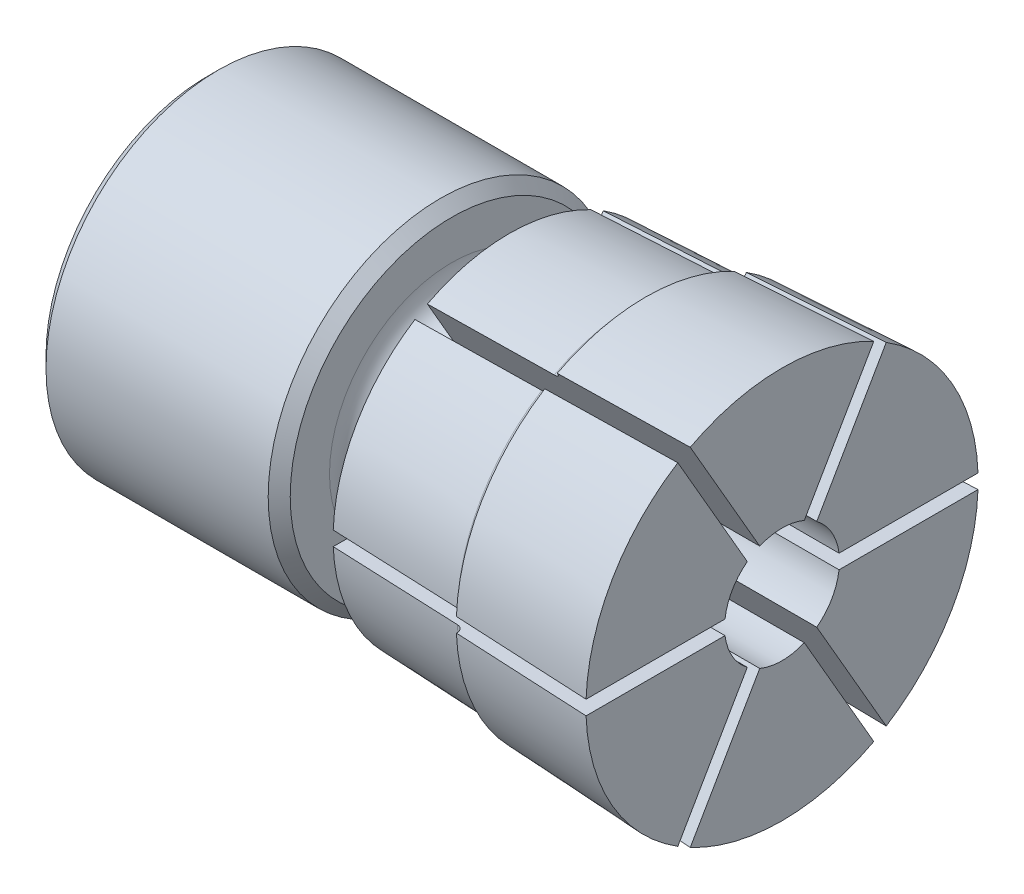
SolidWorks part; units mm, degrees
ref_plane "Front Plane" through (0, 0, 0) normal (0, 0, 1) x (1, 0, 0)
ref_plane "Top Plane" through (0, 0, 0) normal (0, 1, 0) x (1, 0, 0)
ref_plane "Right Plane" through (0, 0, 0) normal (1, 0, 0) x (0, 0, -1)
sketch "Sketch1" plane through (0, 0, 0) normal (0, 0, 1) x (1, 0, 0)
  line L0 (8.054, 0) -> (0, 4.65)
  line L1 (0, 4.65) -> (0, 11.233)
  line L2 (0, 11.233) -> (0.767, 12)
  line L3 (0.767, 12) -> (16.233, 12)
  line L4 (16.233, 12) -> (17, 11.233)
  line L5 (17, 11.233) -> (17, 8.5)
  line L6 (21, 8.5) -> (21, 12.25)
  line L7 (21, 12.25) -> (30.021, 12.6298)
  line L8 (30.5, 13.1294) -> (30.5, 13.175)
  line L9 (30.5, 13.175) -> (40, 13.65)
  line L10 (40, 13.65) -> (40, 0)
  line L11 (40, 0) -> (8.054, 0)
  line L12 (40, 0) -> (8.054, 0) construction
  arc A0 (17, 8.5) -> (21, 8.5) centre (19, 8.5) ccw
  arc A1 (30.021, 12.6298) -> (30.5, 13.1294) centre (30, 13.1294) ccw
revolve "Revolve1" add sketch "Sketch1" angle 360 about L12 reverse direction yes
cosmetic thread "Cosmetic Thread1" parameters "D1"=17, "D2"=22.466
ref_plane "Plane1" through (17.8, 0, 0) normal (1, 0, 0) x (0, 0, -1)
ref_plane "Plane2" through (22.5, 0, 0) normal (1, 0, 0) x (0, 0, -1)
ref_plane "Plane3" through (31, 0, 0) normal (1, 0, 0) x (0, 0, -1)
ref_plane "Plane4" through (33.1, 0, 0) normal (1, 0, 0) x (0, 0, -1)
ref_plane "Plane5" through (41.3, 0, 0) normal (1, 0, 0) x (0, 0, -1)
sketch "Sketch2" plane through (0, 0, 0) normal (1, 0, 0) x (0, 0, -1)
  line L0 (-4, -2.3094) -> (0, -4.6188)
  line L1 (0, -4.6188) -> (4, -2.3094)
  line L2 (4, -2.3094) -> (4, 2.3094)
  line L3 (4, 2.3094) -> (0, 4.6188)
  line L4 (0, 4.6188) -> (-4, 2.3094)
  line L5 (-4, 2.3094) -> (-4, -2.3094)
extrude "Cut-Extrude1" cut sketch "Sketch2" along normal blind 6
sketch "Sketch3" plane through (0, 0, 0) normal (0, 1, 0) x (1, 0, 0)
  line L0 (6, 0) -> (6, 4.75)
  line L1 (6, 4.75) -> (8, 4.75)
  line L2 (8, 4.75) -> (8, 3.5)
  line L3 (8, 3.5) -> (10, 3.5)
  line L4 (10, 3.5) -> (10, 4.2)
  line L5 (10, 4.2) -> (12, 4.2)
  line L6 (12, 4.2) -> (12, 4)
  line L7 (12, 4) -> (42, 4)
  line L8 (42, 4) -> (42, 0)
  line L9 (42, 0) -> (6, 0)
  line L10 (42, 0) -> (6, 0) construction
revolve "Cut-Revolve1" cut sketch "Sketch3" angle 360 about L10 reverse direction yes
ref_plane "Plane6" through (18, 0, 0) normal (1, 0, 0) x (0, 0, -1)
sketch "Sketch4" plane through (18, 0, 0) normal (1, 0, 0) x (0, 0, -1)
  line L0 (-18.65, 0.5) -> (-18.65, -0.5)
  line L1 (-18.65, -0.5) -> (-0.866, -0.5)
  line L2 (-0.866, -0.5) -> (-9.758, -15.9014)
  line L3 (-9.758, -15.9014) -> (-8.892, -16.4014)
  line L4 (-8.892, -16.4014) -> (0, -1)
  line L5 (0, -1) -> (8.892, -16.4014)
  line L6 (8.892, -16.4014) -> (9.758, -15.9014)
  line L7 (9.758, -15.9014) -> (0.866, -0.5)
  line L8 (0.866, -0.5) -> (18.65, -0.5)
  line L9 (18.65, -0.5) -> (18.65, 0.5)
  line L10 (18.65, 0.5) -> (0.866, 0.5)
  line L11 (0.866, 0.5) -> (9.758, 15.9014)
  line L12 (9.758, 15.9014) -> (8.892, 16.4014)
  line L13 (8.892, 16.4014) -> (0, 1)
  line L14 (0, 1) -> (-8.892, 16.4014)
  line L15 (-8.892, 16.4014) -> (-9.758, 15.9014)
  line L16 (-9.758, 15.9014) -> (-0.866, 0.5)
  line L17 (-0.866, 0.5) -> (-18.65, 0.5)
extrude "Cut-Extrude2" cut sketch "Sketch4" along normal blind 40
ref_plane "Plane7" through (40, 0, 0) normal (1, 0, 0) x (0, 0, -1)
ref_plane "ANBAU XY" through (40, 0, 0) normal (1, 0, 0) x (0, 0, -1)
ref_plane "ANBAU XZ" through (0, 0, 0) normal (0, -1, 0) x (-1, 0, 0)
ref_plane "ANBAU YZ" through (0, 0, 0) normal (0, 0, -1) x (-1, 0, 0)
ref_axis "ANBAU X" through (40, 0, 80.9) along (0, 0, -1)
ref_axis "ANBAU Y" through (40, -50, 0) along (0, 1, 0)
ref_axis "ANBAU Z" through (80.9, 0, 0) along (-1, 0, 0)
sketch3d "ANBAU"
  point P0 (40, 0, 0)
other "Freeze***"
